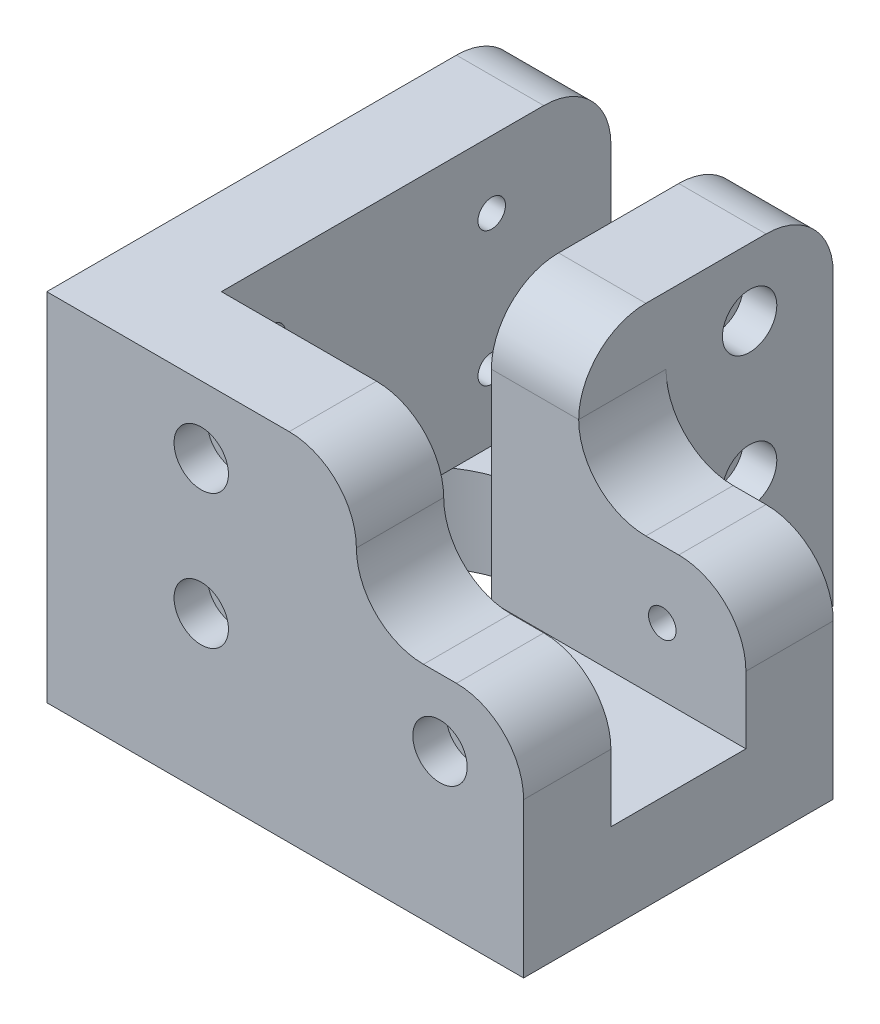
SolidWorks part; units mm, degrees
ref_plane "Alzado" through (0, 0, 0) normal (0, 0, 1) x (1, 0, 0)
ref_plane "Planta" through (0, 0, 0) normal (0, 1, 0) x (1, 0, 0)
ref_plane "Vista lateral" through (0, 0, 0) normal (1, 0, 0) x (0, 0, -1)
sketch "Croquis1" plane through (0, 0, 0) normal (0, 1, 0) x (1, 0, 0)
  line L6 (0, 0) -> (0, 45) construction
  line L7 (0, 45) -> (20.1, 45) construction
  line L8 (20.1, 45) -> (20.1, 20.1) construction
  line L9 (20.1, 20.1) -> (45, 20.1) construction
  line L10 (45, 20.1) -> (45, 0) construction
  line L11 (45, 0) -> (0, 0) construction
  line L12 (-13, -13) -> (-13, 58)
  line L13 (-13, 58) -> (33.1, 58)
  line L14 (33.1, 58) -> (33.1, 33.1)
  line L15 (33.1, 33.1) -> (58, 33.1)
  line L16 (58, 33.1) -> (58, -13)
  line L17 (58, -13) -> (-13, -13)
  dimension "D1" = 20.1
  dimension "D2" = 45
  dimension "D3" = 45
  dimension "D4" = 13
extrude "Saliente-Extruir1" add sketch "Croquis1" along normal blind 13
sketch "Croquis2" plane through (-13, 0, 0) normal (-1, 0, 0) x (0, 0, 1)
  line L0 (13, 13) -> (13, 0) construction
  line L1 (-58, 13) -> (13, 13)
  line L2 (-58, 13) -> (-58, 53)
  line L3 (-58, 53) -> (13, 53)
  line L4 (13, 13) -> (13, 53)
  dimension "D1" = 40
extrude "Saliente-Extruir2" add sketch "Croquis2" against normal blind 13
sketch "Croquis3" plane through (0, 13, 0) normal (0, 1, 0) x (1, 0, 0)
  line L0 (20.1, 58) -> (20.1, 20.1)
  line L1 (33.1, 58) -> (0, 58) construction
  line L2 (20.1, 20.1) -> (58, 20.1)
  line L3 (58, -13) -> (58, 33.1) construction
  line L4 (58, 20.1) -> (58, 33.1)
  line L5 (58, 33.1) -> (33.1, 33.1)
  line L6 (58, 33.1) -> (33.1, 33.1) construction
  line L7 (33.1, 33.1) -> (33.1, 58)
  line L8 (33.1, 58) -> (20.1, 58)
  dimension "D1" = 13
extrude "Saliente-Extruir3" add sketch "Croquis3" along normal up to vertex (40 mm away) up to point (0, 53, 13)
sketch "Croquis4" plane through (0, 0, 13) normal (0, 0, 1) x (1, 0, 0)
  line L0 (0, 53) -> (33.1, 53)
  line L1 (33.1, 53) -> (33.1, 33)
  line L2 (33.1, 33) -> (58, 33)
  line L3 (58, 53) -> (58, 13) construction
  line L4 (58, 33) -> (58, 13)
  line L5 (58, 13) -> (0, 13)
  line L6 (0, 13) -> (0, 53)
  dimension "D1" = 20
  dimension "D2" = 33.1
extrude "Saliente-Extruir4" add sketch "Croquis4" against normal blind 13
sketch "Croquis6" plane through (0, 0, -20.1) normal (0, 0, 1) x (1, 0, 0)
  line L1 (33.1, 53) -> (58, 53)
  line L2 (33.1, 53) -> (33.1, 33)
  line L3 (33.1, 33) -> (58, 33)
  line L4 (58, 53) -> (58, 33)
extrude "Cortar-Extruir1" cut sketch "Croquis6" against normal up to next
sketch "Croquis7" plane through (0, 0, 0) normal (0, 0, -1) x (-1, 0, 0)
  line L0 (0, 13) -> (-58, 13) construction
  line L1 (-45.55, 33) -> (-45.55, 13) construction
  line L2 (-58, 33) -> (-33.1, 33) construction
  circle A0 centre (-45.55, 23) radius 2.05
  dimension "D1" = 4.1
extrude "Cortar-Extruir2" cut sketch "Croquis7" against normal through all both and the other way through all
sketch "Croquis9" plane through (-13, 0, 0) normal (-1, 0, 0) x (0, 0, 1)
  line L0 (-58, 23) -> (13, 23) construction
  line L1 (-58, 53) -> (-58, 0) construction
  line L2 (13, 53) -> (13, 0) construction
  line L3 (-58, 13) -> (-20.1, 13) construction
  line L4 (-22.5, 53) -> (-22.5, 0) construction
  line L5 (13, 53) -> (-58, 53) construction
  line L6 (-58, 0) -> (13, 0) construction
  circle A0 centre (-40.25, 23) radius 2.05
  circle A1 centre (-7.5, 23) radius 2.05
  circle A2 centre (-40.25, 43) radius 2.05
  circle A3 centre (-7.5, 43) radius 2.05
  dimension "D2" = 4.1
  dimension "D1" = 10
  dimension "D3" = 17.75
  dimension "D4" = 20
  dimension "D5" = 15
extrude "Cortar-Extruir3" cut sketch "Croquis9" against normal up to next
sketch "Croquis10" plane through (33.1, 0, 0) normal (1, 0, 0) x (0, 0, -1)
  line L0 (45.55, 0) -> (45.55, 53) construction
  line L1 (33.1, 0) -> (58, 0) construction
  line L2 (20.1, 53) -> (58, 53) construction
  circle A0 centre (45.55, 23) radius 2.05
  circle A1 centre (45.55, 43) radius 2.05
  dimension "D2" = 4.1
  dimension "D1" = 23
  dimension "D3" = 20
extrude "Cortar-Extruir4" cut sketch "Croquis10" against normal up to next
sketch "Croquis12" plane through (0, 0, 13) normal (0, 0, 1) x (1, 0, 0)
  line L0 (45.55, 23) -> (10, 23) construction
  line L1 (10, 23) -> (10, 53) construction
  line L2 (33.1, 53) -> (-13, 53) construction
  line L3 (-13, 53) -> (-13, 0) construction
  circle A0 centre (10, 43) radius 2.05
  circle A1 centre (10, 23) radius 2.05
  dimension "D2" = 4.1
  dimension "D1" = 23
  dimension "D3" = 10
extrude "Cortar-Extruir5" cut sketch "Croquis12" against normal up to next
sketch "Croquis13" plane through (0, 0, 13) normal (0, 0, 1) x (1, 0, 0)
  circle A0 centre (10, 43) radius 4.05
  circle A1 centre (10, 23) radius 4.05
  circle A2 centre (45.55, 23) radius 4.05
  dimension "D1" = 8.1
extrude "Cortar-Extruir6" cut sketch "Croquis13" against normal blind 5
sketch "Croquis14" plane through (33.1, 0, 0) normal (1, 0, 0) x (0, 0, -1)
  circle A0 centre (45.55, 43) radius 4.05
  circle A1 centre (45.55, 23) radius 4.05
  dimension "D1" = 8.1
extrude "Cortar-Extruir7" cut sketch "Croquis14" against normal blind 5
sketch "Croquis15" plane through (-13, 0, 0) normal (-1, 0, 0) x (0, 0, 1)
  circle A0 centre (-40.25, 43) radius 4.05
  circle A1 centre (-40.25, 23) radius 4.05
  circle A2 centre (-7.5, 23) radius 4.05
  circle A3 centre (-7.5, 43) radius 4.05
  dimension "D1" = 8.1
extrude "Cortar-Extruir8" cut sketch "Croquis15" against normal blind 5
sketch "Croquis16" plane through (0, 0, -33.1) normal (0, 0, -1) x (-1, 0, 0)
  circle A0 centre (-45.55, 23) radius 4.05
  dimension "D1" = 8.1
extrude "Cortar-Extruir9" cut sketch "Croquis16" against normal blind 5
fillet "Redondeo1" radius 10 8 edges at (26.6, 53, -20.1) (26.6, 53, -58) (-6.5, 53, -58) (58, 33, -26.6) (58, 33, 6.5) (33.1, 53, 6.5) (33.1, 33, -26.6) (33.1, 33, 6.5)
sketch "Croquis17" plane through (0, 0, 0) normal (0, -1, 0) x (1, 0, 0)
  circle A0 centre (10.05, -19.55) radius 18
  dimension "D1" = 36
extrude "Cortar-Extruir10" cut sketch "Croquis17" against normal blind 13
